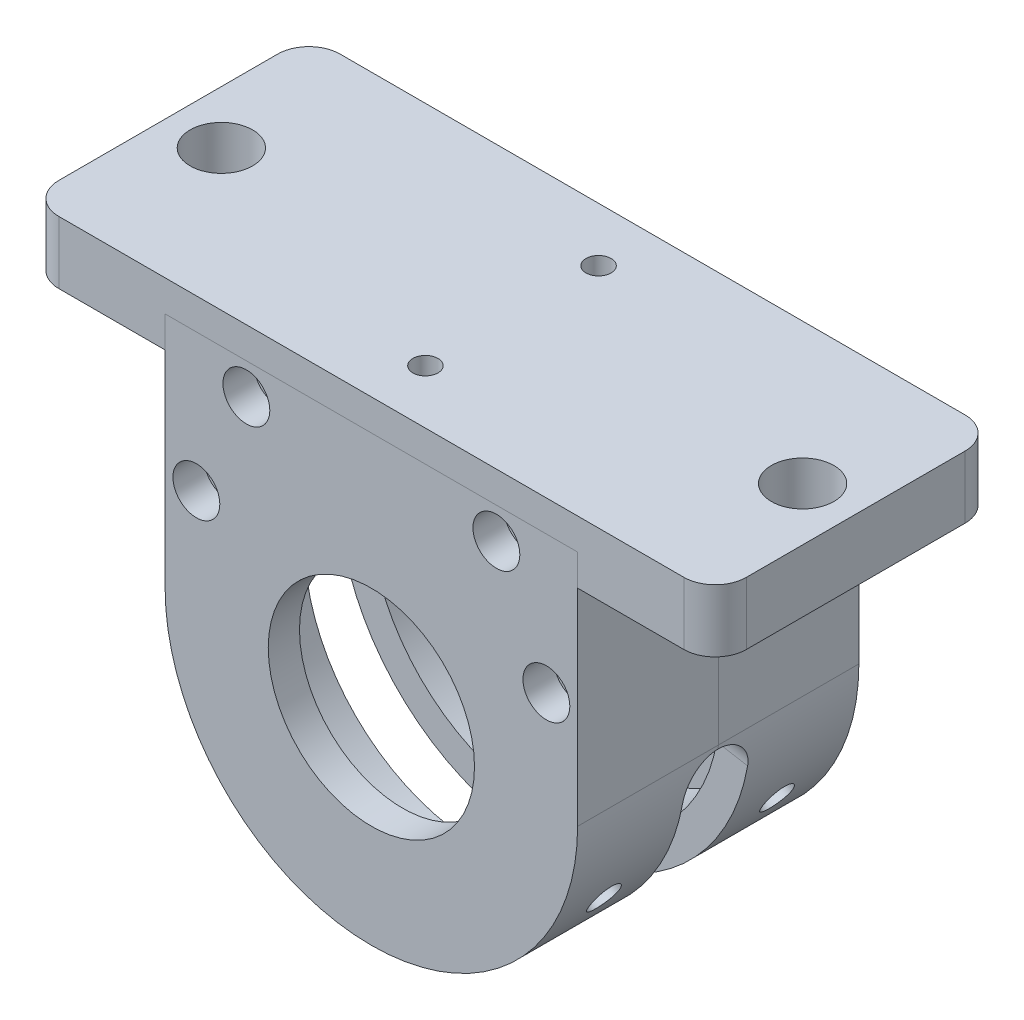
SolidWorks part; units mm, degrees
material "1060 Alloy"
ref_plane "Front Plane" through (0, 0, 0) normal (0, 0, 1) x (1, 0, 0)
ref_plane "Top Plane" through (0, 0, 0) normal (0, 1, 0) x (1, 0, 0)
ref_plane "Right Plane" through (0, 0, 0) normal (1, 0, 0) x (0, 0, -1)
sketch "Sketch1" plane through (0, 0, 0) normal (0, 0, 1) x (1, 0, 0)
  line L0 (0, 0) -> (0, -83.82) construction
  line L1 (-69.85, 0) -> (69.85, 0) construction
  line L2 (-41.91, -41.91) -> (-41.91, 0)
  line L3 (-69.85, 0) -> (-41.91, 0)
  line L4 (-69.85, 0) -> (-69.85, 12.7)
  line L5 (-69.85, 12.7) -> (69.85, 12.7)
  line L6 (69.85, 0) -> (69.85, 12.7)
  line L7 (41.91, -41.91) -> (41.91, 0)
  line L8 (41.91, 0) -> (69.85, 0)
  line L9 (0, 0) -> (41.91, 0) construction
  line L10 (-41.91, 0) -> (0, 0) construction
  arc A0 (-41.91, -41.91) -> (41.91, -41.91) centre (0, -41.91) ccw
  arc A1 (0, 0) -> (-41.91, -41.91) centre (0, -41.91) ccw construction
  arc A2 (41.91, -41.91) -> (0, 0) centre (0, -41.91) ccw construction
  point P6 (0, 0)
  dimension "D2" = 41.91
  dimension "D1" = 139.7
  dimension "D3" = 12.7
sketch "Tube Reference Geometry" plane through (0, 0, 0) normal (0, 0, 1) x (1, 0, 0)
  circle A0 centre (0, -41.91) radius 19.05 construction
  circle A1 centre (0, -41.91) radius 15.875 construction
  dimension "D1" = 38.1
  dimension "D2" = 3.175
extrude "Boss-Extrude1" add sketch "Sketch1" along normal blind 57.15
fillet "Fillet1" radius 6.35 4 edges at (69.85, 6.35, 57.15) (69.85, 6.35, 0) (-69.85, 6.35, 0) (-69.85, 6.35, 57.15)
sketch "Sketch3" plane through (0, 0, 0) normal (0, -1, 0) x (1, 0, 0)
  line L0 (-69.85, 50.8) -> (-69.85, 6.35) construction
  line L1 (69.85, 50.8) -> (69.85, 6.35) construction
  circle A0 centre (-59.055, 28.575) radius 6.35
  circle A1 centre (59.055, 28.575) radius 6.35
  point P8 (-69.85, 28.575)
  dimension "D1" = 12.7
  dimension "D2" = 10.795
  dimension "D3" = 10.795
extrude "Cut-Extrude1" cut sketch "Sketch3" against normal blind 50.8
sketch "Sketch4" plane through (0, 0, 57.15) normal (0, 0, 1) x (1, 0, 0)
  circle A4 centre (0, -41.91) radius 20.955
  circle A5 centre (0, -41.91) radius 20.955
  dimension "D1" = 1.905
ref_plane "Plane4" through (0, 0, 28.575) normal (0, 0, 1) x (1, 0, 0)
extrude "Cut-Extrude2" cut sketch "Sketch4" against normal through all
sketch "Sketch6" plane through (0, 0, 28.575) normal (0, 0, 1) x (1, 0, 0)
  line L0 (-41.2733, -49.1876) -> (-20.6366, -45.5488)
  line L1 (-41.2733, -49.1876) -> (0, -41.91) construction
  line L2 (0, -41.91) -> (41.2733, -49.1876) construction
  line L3 (0, 0) -> (0, -41.91) construction
  line L4 (41.2733, -49.1876) -> (20.6366, -45.5488)
  arc A0 (-41.91, -41.91) -> (41.91, -41.91) centre (0, -41.91) ccw construction
  circle A1 centre (0, -41.91) radius 20.955 construction
  arc A2 (-41.2733, -49.1876) -> (41.2733, -49.1876) centre (0, -41.91) ccw
  arc A3 (-20.6366, -45.5488) -> (20.6366, -45.5488) centre (0, -41.91) ccw
  arc A4 (0, -20.955) -> (-20.6366, -45.5488) centre (0, -41.91) ccw construction
  arc A5 (20.6366, -45.5488) -> (0, -20.955) centre (0, -41.91) ccw construction
  arc A6 (41.2733, -49.1876) -> (41.91, -41.91) centre (0, -41.91) ccw construction
  arc A7 (-41.91, -41.91) -> (-41.2733, -49.1876) centre (0, -41.91) ccw construction
  dimension "D1" = 160
  dimension "D2" = 100
extrude "Cut-Extrude3" cut sketch "Sketch6" against normal mid plane 13.208
ref_axis "Axis1" through (-20.6366, -45.5488, 28.575) along (-0.9848, -0.1736, 0)
ref_axis "Axis2" through (-108.095, -22.8499, 28.575) along (0.9848, -0.1736, 0)
ref_plane "Plane5" through (48.4403, -8.5413, 0) normal (0.9848, -0.1736, 0) x (0, 0, -1)
sketch "Sketch8" plane through (48.4403, -8.5413, 0) normal (0.9848, -0.1736, 0) x (0, 0, -1)
  line L0 (-21.971, -41.2733) -> (-35.179, -41.2733) construction
  line L1 (-35.179, -62.2283) -> (-35.179, -41.2733) construction
  line L2 (-35.179, -41.2733) -> (-21.971, -41.2733)
  arc A0 (-21.971, -41.2733) -> (-35.179, -41.2733) centre (-28.575, -41.2733) ccw
extrude "Cut-Extrude4" cut sketch "Sketch8" against normal up to next
mirror "Mirror1" about plane through (0, 0, 0) normal (1, 0, 0) of "Cut-Extrude4"
sketch "Sketch10" plane through (0, 0, 0) normal (0, 0, -1) x (-1, 0, 0)
  circle A0 centre (0, -41.91) radius 35.56
  arc A1 (-41.91, -41.91) -> (41.91, -41.91) centre (0, -41.91) ccw construction
  dimension "D1" = 6.35
extrude "Cut-Extrude6" cut sketch "Sketch10" against normal through all from offset 6.35 offset against normal yes
ref_plane "Plane6" through (0, 0, 28.575) normal (0, 0, -1) x (-1, 0, 0)
sketch "Sketch19" plane through (0, 0, 28.575) normal (0, 0, -1) x (-1, 0, 0)
  line L0 (-41.91, -41.91) -> (-41.91, 0) construction
  line L1 (41.91, 6.35) -> (-41.91, 6.35)
  line L2 (41.91, 6.35) -> (41.91, -83.82)
  line L3 (41.91, -83.82) -> (-41.91, -83.82)
  line L4 (-41.91, 6.35) -> (-41.91, -83.82)
  line L5 (63.5, 0) -> (41.91, 0) construction
  arc A0 (-41.91, -41.91) -> (41.91, -41.91) centre (0, -41.91) ccw construction
  point P4 (0, 6.35)
  dimension "D1" = 6.35
split "Split2" trim tools "Sketch19" bodies to split 108 109 resulting bodies 116 117
sketch "Sketch20" plane through (0, 0, 28.575) normal (0, 0, -1) x (-1, 0, 0)
  line L1 (-41.91, -83.82) -> (41.91, -83.82)
  line L2 (-41.91, -83.82) -> (-41.91, 6.35)
  line L3 (-41.91, 6.35) -> (41.91, 6.35)
  line L4 (41.91, -83.82) -> (41.91, 6.35)
extrude "Cut-Extrude8" cut sketch "Sketch20" against normal through all
mirror "Mirror3" about plane through (0, 0, 28.575) normal (0, 0, 1) of bodies 118
sketch "Sketch21" plane through (0, 0, 57.15) normal (0, 0, 1) x (1, 0, 0)
  line L0 (41.91, 6.35) -> (-41.91, 6.35) construction
  line L1 (0, 0) -> (0, -83.82) construction
  arc A0 (-35.0198, -48.0849) -> (35.0198, -48.0849) centre (0, -41.91) ccw construction
  arc A1 (-35.0198, -48.0849) -> (35.0198, -48.0849) centre (0, -41.91) ccw
  arc A2 (-41.91, -41.91) -> (41.91, -41.91) centre (0, -41.91) ccw construction
  circle A3 centre (0, -41.91) radius 35.56
  circle A4 centre (0, -41.91) radius 35.56 construction
  point P4 (-35.56, -21.59)
  point P6 (-25.4, 0)
  point P16 (35.56, -21.59)
  point P18 (25.4, 0)
  dimension "D2" = 25.4
  dimension "D3" = 35.56
  dimension "D4" = 6.35
  dimension "D5" = 27.94
  dimension "D1" = 0
hole_wizard "CBORE for 1/4 Socket Head Cap Screw1 for 92196A434" positions "Sketch24" profile "Sketch25" counterbore size "1/4" standard "ANSI Inch" end condition through all
sketch "Sketch24" plane through (0, 0, 57.15) normal (0, 0, 1) x (1, 0, 0)
  point P0 (-35.56, -21.59)
  point P6 (35.56, -21.59)
  point P10 (-25.4, 0)
  point P13 (25.4, 0)
sketch "Sketch25" plane through (-35.56, -21.59, 57.15) normal (1, 0, 0) x (0, -1, 0)
  line L0 (0, 0) -> (0, 57.15)
  line L1 (0, 57.15) -> (3.175, 57.15)
  line L3 (3.175, 57.15) -> (3.175, 6.35)
  line L4 (3.175, 6.35) -> (4.7625, 6.35)
  line L5 (4.7625, 6.35) -> (4.7625, 0)
  line L7 (4.7625, 0) -> (0, 0)
  line L11 (0, -6.35) -> (0, 107.95) construction
  dimension "Thru Hole Dia." = 6.35
  dimension "Thru Hole Depth" = 57.15
  dimension "C'Bore Dia." = 9.525
  dimension "C'Bore Depth" = 6.35
sketch "Sketch26" plane through (0, 12.7, 0) normal (0, 1, 0) x (1, 0, 0)
  line L6 (-41.2733, -21.971) -> (41.2733, -21.971) construction
  line L7 (-69.85, -21.971) -> (69.85, -21.971)
  line L8 (41.2733, -35.179) -> (-41.2733, -35.179) construction
  line L9 (69.85, -35.179) -> (-69.85, -35.179) construction
  line L12 (-69.85, -50.8) -> (-69.85, -6.35) construction
  line L13 (69.85, -50.8) -> (69.85, -6.35) construction
  line L14 (-69.85, -10.9855) -> (69.85, -10.9855) construction
  line L16 (-69.85, 0) -> (69.85, 0) construction
  line L17 (29.77, -28.575) -> (-29.77, -28.575) construction
  point P0 (0, -10.9855)
  point P24 (0, -46.1645)
hole_wizard "1/4-20 Tapped Hole1" positions "Sketch27" profile "Sketch28" tap size "1/4-20" standard "ANSI Inch"
sketch "Sketch27" plane through (0, 12.7, 0) normal (0, 1, 0) x (1, 0, 0)
  point P0 (0, -10.9855)
  point P3 (0, -46.1645)
cosmetic thread "Hole Thread1" parameters "D1"=6.35, "D2"=6.35
cosmetic thread "Hole Thread2" parameters "D1"=6.35, "D2"=6.35
sketch "Sketch28" plane through (0, 12.7, 10.9855) normal (1, 0, 0) x (0, 0, 1)
  line L0 (0, 0) -> (0, 21.8538)
  line L1 (0, 21.8538) -> (2.5527, 20.32)
  line L2 (2.5527, 20.32) -> (2.5527, 0)
  line L5 (2.5527, 0) -> (0, 0)
  line L10 (0, 21.8538) -> (-2.5527, 20.32) construction
  line L11 (0, -6.35) -> (0, 107.95) construction
  dimension "Tap Drill Dia." = 5.1054
  dimension "Tap Drill Depth" = 20.32
  dimension "Drill Angle" = 118
ref_plane "Plane7" through (54.4427, -31.4325, 0) normal (0.866, -0.5, 0) x (0, 0, 1)
sketch "Sketch29" plane through (54.4427, -31.4325, 0) normal (0.866, -0.5, 0) x (0, 0, 1)
  line L0 (57.15, 15.3401) -> (57.15, 78.2051) construction
  line L1 (57.15, 36.2951) -> (35.179, 36.2951) construction
  line L2 (35.179, 78.2051) -> (35.179, 21.9611) construction
  point P0 (57.15, 36.2951)
  point P10 (46.1645, 36.2951)
sketch "Sketch31" plane through (54.4427, -31.4325, 0) normal (0.866, -0.5, 0) x (0, 0, 1)
  line L2 (0, 78.2051) -> (21.971, 78.2051) construction
  circle A0 centre (46.1645, 36.2951) radius 3.175
  circle A1 centre (10.9855, 36.2951) radius 3.175
  point P5 (10.9855, 78.2051)
  point P6 (0, 0)
  dimension "D1" = 6.35
extrude "Cut-Extrude9" cut sketch "Sketch31" against normal up to surface (6.492 mm away) up to face at (-0.5797, -6.3547, 43.6785)
mirror "Mirror4" about plane through (0, 0, 0) normal (1, 0, 0) of "Cut-Extrude9"
equation "\"Overall Width\"= 5.5in"
equation "\"Overall Height\"= 2.25in"
equation "\"Overall Length\"= 3in"
equation "\"D1@Sketch1\"=\"Overall Width\""
equation "\"D1@Boss-Extrude1\"=\"Overall Height\""
